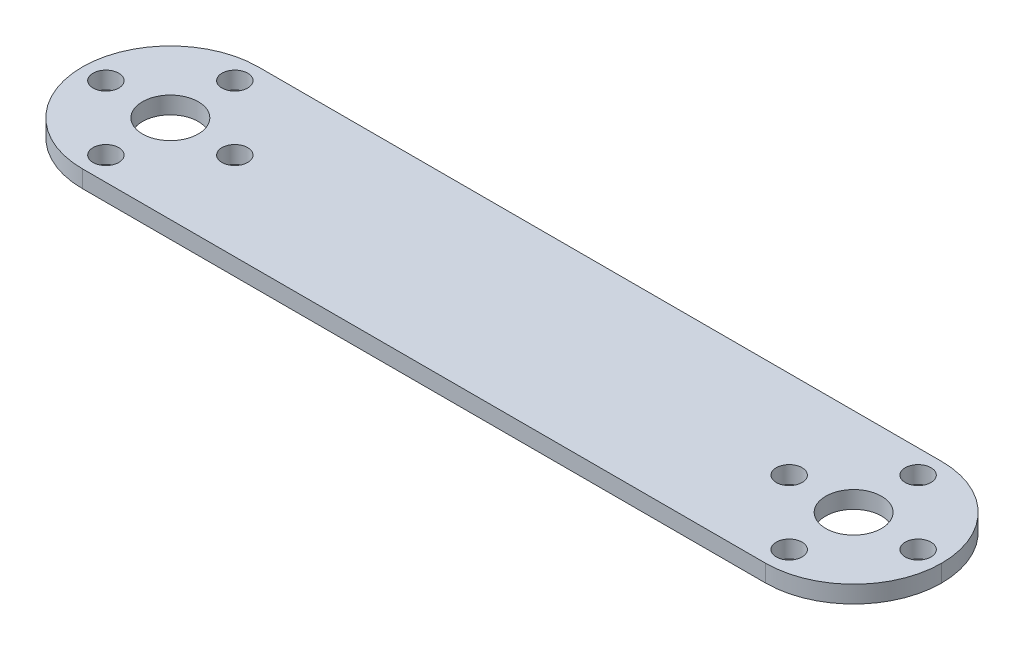
SolidWorks part; units mm, degrees
ref_plane "Front Plane" through (0, 0, 0) normal (0, 0, 1) x (1, 0, 0)
ref_plane "Top Plane" through (0, 0, 0) normal (0, 1, 0) x (1, 0, 0)
ref_plane "Right Plane" through (0, 0, 0) normal (1, 0, 0) x (0, 0, -1)
sketch "Sketch1" plane through (0, 0, 0) normal (0, 1, 0) x (1, 0, 0)
  line L0 (0, 10.25) -> (100, 10.25) construction
  line L1 (0, 0) -> (100, 0)
  line L2 (0, 0) -> (0, 20.5)
  line L3 (0, 20.5) -> (100, 20.5)
  line L4 (100, 0) -> (100, 20.5)
  line L5 (50, 20.5) -> (50, 0) construction
  line L6 (10.25, 10.25) -> (16.2336, 16.2336) construction
  line L7 (10.25, 10.25) -> (15.5852, 4.9148) construction
  circle A0 centre (10.25, 10.25) radius 3.25
  circle A1 centre (17.75, 10.25) radius 1.5
  circle A2 centre (10.25, 17.75) radius 1.5
  circle A3 centre (10.25, 2.75) radius 1.5
  circle A4 centre (2.75, 10.25) radius 1.5
  circle A5 centre (82.25, 10.25) radius 1.5
  circle A6 centre (89.75, 17.75) radius 1.5
  circle A7 centre (89.75, 2.75) radius 1.5
  circle A8 centre (97.25, 10.25) radius 1.5
  circle A9 centre (89.75, 10.25) radius 3.25
  dimension "D3" = 6.5
  dimension "D4" = 3
  dimension "D6" = 7.5
  dimension "D1" = 100
  dimension "D2" = 20.5
  dimension "D5" = 10.25
extrude "Boss-Extrude1" add sketch "Sketch1" along normal blind 2
fillet "Fillet1" radius 10.25 4 edges at (0, 1, 0) (0, 1, -20.5) (100, 1, -20.5) (100, 1, 0)
